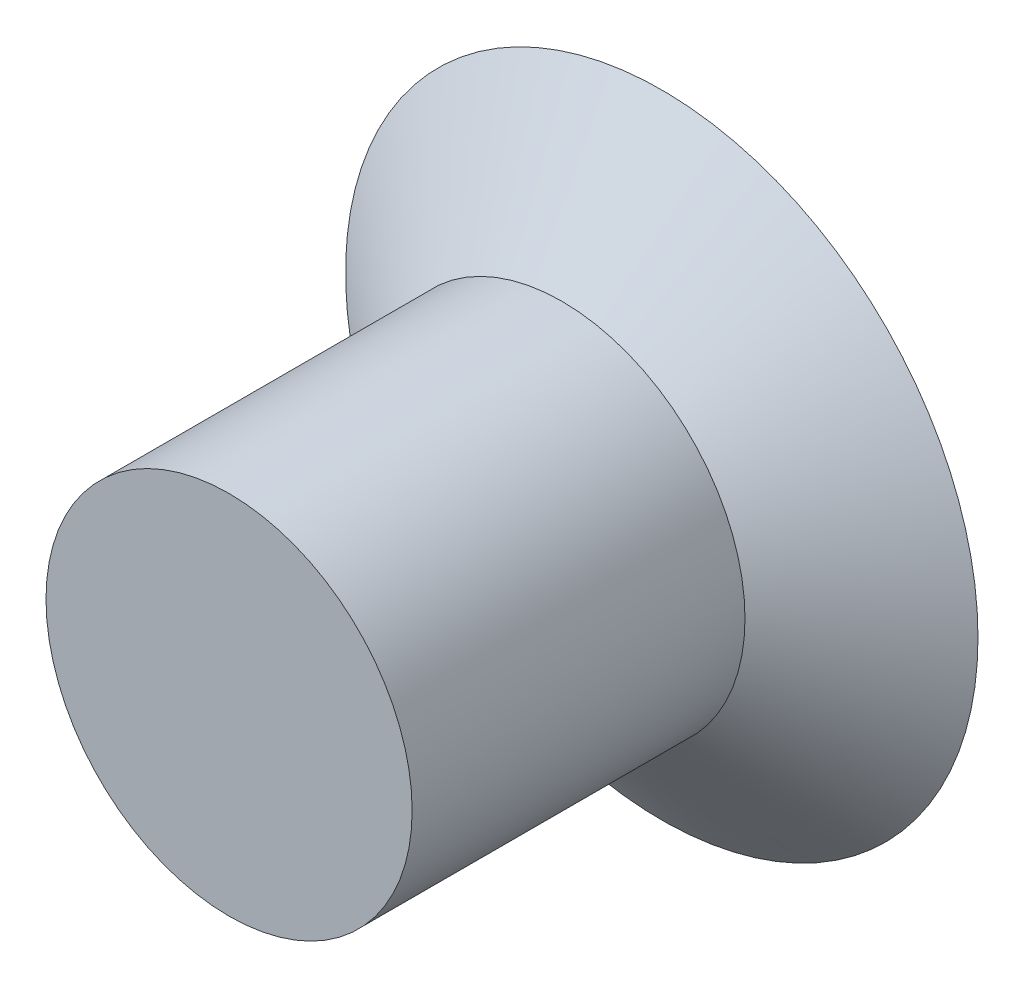
SolidWorks part; units mm, degrees
ref_plane "Front Plane" through (0, 0, 0) normal (0, 0, 1) x (1, 0, 0)
ref_plane "Top Plane" through (0, 0, 0) normal (0, 1, 0) x (1, 0, 0)
ref_plane "Right Plane" through (0, 0, 0) normal (1, 0, 0) x (0, 0, -1)
sketch "Sketch1" plane through (0, 0, 0) normal (0, 0, 1) x (1, 0, 0)
  circle A0 centre (0, 0) radius 9.5
  dimension "D1" = 19
ref_plane "Plane1" through (0, 0, 3) normal (0, 0, 1) x (1, 0, 0)
sketch "Sketch2" plane through (0, 0, 3) normal (0, 0, 1) x (1, 0, 0)
  circle A0 centre (0, 0) radius 5.5
  dimension "D1" = 11
loft "Loft1" add profiles "Sketch2", "Sketch1" connector at (5.1188, -2.0118, 3) connector at (8.3249, -4.5767, 0)
extrude "Boss-Extrude1" add sketch "Sketch2<2>" along normal blind 10
sketch "Sketch2<2>" plane through (0, 0, 3) normal (0, 0, 1) x (1, 0, 0) same geometry as "Sketch2"
